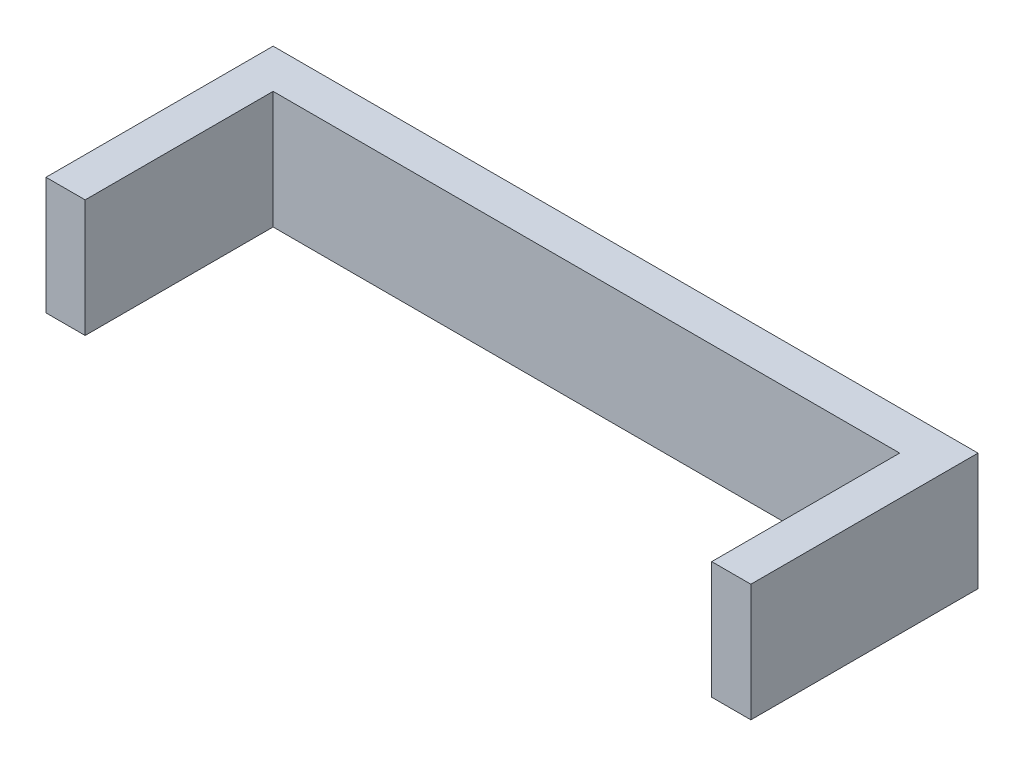
SolidWorks part; units mm, degrees
ref_plane "Front Plane" through (0, 0, 0) normal (0, 0, 1) x (1, 0, 0)
ref_plane "Top Plane" through (0, 0, 0) normal (0, 1, 0) x (1, 0, 0)
ref_plane "Right Plane" through (0, 0, 0) normal (1, 0, 0) x (0, 0, -1)
sketch "Sketch1" plane through (0, 0, 0) normal (0, 1, 0) x (1, 0, 0)
  line L0 (-35, 50) -> (35, 50)
  line L5 (50, 35) -> (50, -35)
  line L6 (-50, 35) -> (-50, -35)
  line L7 (-35, -50) -> (35, -50)
  arc A0 (35, -50) -> (50, -35) centre (35, -35) ccw
  arc A1 (-50, -35) -> (-35, -50) centre (-35, -35) ccw
  arc A2 (-50, 35) -> (-35, 50) centre (-35, 35) cw
  arc A3 (35, 50) -> (50, 35) centre (35, 35) cw
  point P14 (0, -50)
  point P19 (-50, 0)
  dimension "D3" = 15
  dimension "D4" = 15
  dimension "D5" = 15
  dimension "D6" = 15
  dimension "D1" = 100
  dimension "D2" = 100
extrude "Boss-Extrude1" add sketch "Sketch1" along normal blind 10
sketch "Sketch2" plane through (0, 10, 0) normal (0, 1, 0) x (1, 0, 0)
  line L0 (-50, 35) -> (-50, -35) construction
  line L1 (-42, 40) -> (-24.8, 40)
  line L2 (-42, 40) -> (-42, -3)
  line L3 (-42, -3) -> (-24.8, -3)
  line L4 (-24.8, 40) -> (-24.8, -3)
  line L5 (-42, 40) -> (-24.8, -3) construction
  line L6 (-42, -3) -> (-24.8, 40) construction
  line L7 (24.8, 40) -> (42, 40)
  line L8 (24.8, 40) -> (24.8, -3)
  line L9 (24.8, -3) -> (42, -3)
  line L10 (42, 40) -> (42, -3)
  line L11 (24.8, 40) -> (42, -3) construction
  line L12 (24.8, -3) -> (42, 40) construction
  line L13 (50, -35) -> (50, 35) construction
  line L15 (35, 50) -> (-35, 50) construction
  point P0 (-33.4, 18.5)
  point P5 (33.4, 18.5)
  dimension "D1" = 8
  dimension "D2" = 8
  dimension "D3" = 17.2
  dimension "D4" = 17.2
  dimension "D5" = 43
  dimension "D6" = 43
  dimension "D7" = 10
  dimension "D8" = 10
extrude "Cut-Extrude1" cut sketch "Sketch2" against normal through all
sketch "Sketch3" plane through (0, 10, 0) normal (0, 1, 0) x (1, 0, 0)
  line L1 (-40, -8) -> (40, -8)
  line L2 (-40, -8) -> (-40, -32)
  line L3 (-40, -32) -> (40, -32)
  line L4 (40, -8) -> (40, -32)
  line L5 (-40, -8) -> (40, -32) construction
  line L6 (-40, -32) -> (40, -8) construction
  line L7 (-45, -3) -> (45, -3)
  line L8 (-45, -3) -> (-45, -37)
  line L9 (-45, -37) -> (45, -37)
  line L10 (45, -3) -> (45, -37)
  line L11 (-45, -3) -> (45, -37) construction
  line L12 (-45, -37) -> (45, -3) construction
  line L13 (-35, -50) -> (35, -50) construction
  line L14 (-42, -3) -> (-24.8, -3) construction
  point P0 (0, -20)
  point P5 (0, -20)
  point P18 (0, -50)
  dimension "D1" = 24
  dimension "D2" = 80
  dimension "D3" = 34
  dimension "D4" = 90
extrude "Boss-Extrude3" add sketch "Sketch3" along normal blind 15
sketch "Sketch4" plane through (0, 10, 0) normal (0, 1, 0) x (1, 0, 0)
  line L0 (24.8, 40) -> (24.8, -3) construction
  line L3 (-24.8, 12.5) -> (24.8, 12.5)
  line L5 (-24.8, 24.5) -> (24.8, 24.5)
  line L6 (-24.8, 29.5) -> (24.8, 29.5)
  line L11 (-24.8, 7.5) -> (24.8, 7.5)
  line L12 (-24.8, 29.5) -> (-24.8, 24.5)
  line L13 (-24.8, -3) -> (-24.8, 40) construction
  line L14 (-24.8, 12.5) -> (-24.8, 7.5)
  line L15 (24.8, 12.5) -> (24.8, 7.5)
  line L16 (24.8, 29.5) -> (24.8, 24.5)
  point P4 (-24.8, 18.5)
  dimension "D1" = 5
  dimension "D2" = 12
  dimension "D3" = 5
  dimension "D4" = 6
extrude "Boss-Extrude4" add sketch "Sketch4" along normal blind 10
sketch "Sketch5" plane through (0, 20, 0) normal (0, 1, 0) x (1, 0, 0)
  line L0 (-24.8, 7.5) -> (24.8, 7.5) construction
  line L1 (-24.8, 29.5) -> (-9.8, 29.5)
  line L2 (-24.8, 29.5) -> (-24.8, 7.5)
  line L3 (-24.8, 7.5) -> (-9.8, 7.5)
  line L4 (-9.8, 29.5) -> (-9.8, 7.5)
  line L6 (24.8, 29.5) -> (9.8, 29.5)
  line L7 (24.8, 29.5) -> (24.8, 7.5)
  line L8 (24.8, 7.5) -> (9.8, 7.5)
  line L9 (9.8, 29.5) -> (9.8, 7.5)
  dimension "D1" = 15
  dimension "D2" = 15
extrude "Boss-Extrude5" add sketch "Sketch5" along normal blind 5
sketch "Sketch6" plane through (0, 10, 0) normal (0, 1, 0) x (1, 0, 0)
  line L1 (-45, -37) -> (45, -37)
  line L2 (-45, -37) -> (-45, 40)
  line L3 (-45, 40) -> (45, 40)
  line L4 (45, -37) -> (45, 40)
  line L5 (45, -37) -> (45, -3) construction
  line L6 (-24.8, 40) -> (-42, 40) construction
  line L7 (-50, 35) -> (-50, -35) construction
  line L8 (-35, -50) -> (35, -50) construction
  line L9 (50, -35) -> (50, 35) construction
  line L10 (35, 50) -> (-35, 50) construction
  line L11 (-50, 35) -> (-50, -35)
  line L12 (-35, -50) -> (35, -50)
  line L13 (50, -35) -> (50, 35)
  line L14 (35, 50) -> (-35, 50)
  arc A0 (-50, -35) -> (-35, -50) centre (-35, -35) ccw construction
  arc A1 (35, -50) -> (50, -35) centre (35, -35) ccw construction
  arc A2 (50, 35) -> (35, 50) centre (35, 35) ccw construction
  arc A3 (-35, 50) -> (-50, 35) centre (-35, 35) ccw construction
  arc A4 (-50, -35) -> (-35, -50) centre (-35, -35) ccw
  arc A5 (35, -50) -> (50, -35) centre (35, -35) ccw
  arc A6 (50, 35) -> (35, 50) centre (35, 35) ccw
  arc A7 (-35, 50) -> (-50, 35) centre (-35, 35) ccw
extrude "Boss-Extrude6" add sketch "Sketch6" along normal up to surface (15 mm away) up to face at (0, 25, 20)
sketch "Sketch9" plane through (0, 25, 0) normal (0, 1, 0) x (1, 0, 0)
  line L22 (-50, 35) -> (-50, -35) construction
  line L23 (-35, -50) -> (35, -50) construction
  line L24 (50, -35) -> (50, 35) construction
  line L25 (35, 50) -> (-35, 50) construction
  line L26 (-45, 35) -> (-45, -35)
  line L27 (-35, -45) -> (35, -45)
  line L28 (45, -35) -> (45, 35)
  line L29 (35, 45) -> (-35, 45)
  line L30 (-45, 35) -> (-45, -32)
  line L32 (45, -32) -> (45, 35)
  line L34 (-50, 35) -> (-50, -35)
  line L35 (-35, -50) -> (35, -50)
  line L36 (50, -35) -> (50, 35)
  line L37 (35, 50) -> (-35, 50)
  line L38 (45, -32) -> (-45, -32)
  line L39 (-40, -32) -> (40, -32) construction
  line L40 (43.6603, 40) -> (-43.6603, 40)
  line L41 (45, 40) -> (-45, 40) construction
  arc A23 (-50, -35) -> (-35, -50) centre (-35, -35) ccw construction
  arc A24 (35, -50) -> (50, -35) centre (35, -35) ccw construction
  arc A25 (50, 35) -> (35, 50) centre (35, 35) ccw construction
  arc A26 (-35, 50) -> (-50, 35) centre (-35, 35) ccw construction
  arc A27 (-45, -35) -> (-35, -45) centre (-35, -35) ccw
  arc A28 (35, -45) -> (45, -35) centre (35, -35) ccw
  arc A29 (45, 35) -> (35, 45) centre (35, 35) ccw
  arc A30 (-35, 45) -> (-45, 35) centre (-35, 35) ccw
  arc A33 (45, 35) -> (43.6603, 40) centre (35, 35) ccw
  arc A34 (-43.6603, 40) -> (-45, 35) centre (-35, 35) ccw
  arc A35 (-50, -35) -> (-35, -50) centre (-35, -35) ccw
  arc A36 (35, -50) -> (50, -35) centre (35, -35) ccw
  arc A37 (50, 35) -> (35, 50) centre (35, 35) ccw
  arc A38 (-35, 50) -> (-50, 35) centre (-35, 35) ccw
  dimension "D1" = 5
extrude "Boss-Extrude8" add sketch "Sketch9" along normal blind 39
chamfer "Chamfer1" distance 64 angle 3 8 edges at (0, 64, 50) (45.6066, 64, 45.6066) (-45.6066, 64, 45.6066) (50, 64, 0) (-50, 64, 0) (45.6066, 64, -45.6066) (-45.6066, 64, -45.6066) (0, 64, -50) first distance on face at (0, 32, 50) first distance on face at (44.0533, 32, 44.0533) first distance on face at (-44.0533, 32, 44.0533) first distance on face at (50, 32, 0) first distance on face at (-50, 32, 0) first distance on face at (44.0533, 32, -44.0533) first distance on face at (-44.0533, 32, -44.0533) first distance on face at (0, 32, -50)
chamfer "Chamfer2" distance 64 angle 10 1 edges at (0, 64, -46.6459) tangent propagation no first distance on face at (0, 32, -48.323)
chamfer "Chamfer3" distance 64 angle 12 1 edges at (0, 64, 46.6459) tangent propagation no first distance on face at (0, 32, 48.323)
sketch "Sketch10" plane through (0, 1.3075, 0) normal (-1, 0, 0) x (0, 0, 1)
  line L0 (-35, 62.6925) -> (32.8702, 62.6925) construction
  line L1 (2.8702, 62.6925) -> (-47.1298, 62.6925)
  line L2 (2.8702, 62.6925) -> (2.8702, 35.6925)
  line L3 (2.8702, 35.6925) -> (-47.1298, 35.6925)
  line L4 (-47.1298, 62.6925) -> (-47.1298, 35.6925)
  dimension "D1" = 50
  dimension "D2" = 27
  dimension "D3" = 30
extrude "Cut-Extrude3" cut sketch "Sketch10" against normal through all and the other way through all
sketch "Sketch11" plane through (0, 10, 0) normal (0, 1, 0) x (1, 0, 0)
  line L0 (24.8, 29.5) -> (-24.8, 29.5) construction
  line L1 (-22.75, 29.5) -> (22.75, 29.5)
  line L2 (-22.75, 29.5) -> (-22.75, 40)
  line L3 (-22.75, 40) -> (22.75, 40)
  line L4 (22.75, 29.5) -> (22.75, 40)
  line L5 (43.6603, 40) -> (-43.6603, 40) construction
  line L9 (24.8, 40) -> (-24.8, 40) construction
  point P10 (0, 40)
  point P11 (0, 29.5)
  dimension "D1" = 45.5
extrude "Cut-Extrude4" cut sketch "Sketch11" against normal blind 7.5
sketch "Sketch14" plane through (0, 10, 0) normal (0, 1, 0) x (1, 0, 0)
  line L0 (-24.8, 29.5) -> (-22.75, 29.5) construction
  line L1 (-22.75, 29.5) -> (-22.75, 40) construction
  line L2 (-22.75, 40) -> (-24.8, 40) construction
  line L3 (-24.8, 40) -> (-24.8, 29.5) construction
  line L4 (24.8, 40) -> (22.75, 40) construction
  line L5 (22.75, 40) -> (22.75, 29.5) construction
  line L6 (22.75, 29.5) -> (24.8, 29.5) construction
  line L7 (24.8, 29.5) -> (24.8, 40) construction
  line L8 (-24.8, 29.5) -> (-22.75, 29.5)
  line L9 (-22.75, 29.5) -> (-22.75, 40)
  line L10 (-22.75, 40) -> (-24.8, 40)
  line L11 (-24.8, 40) -> (-24.8, 29.5)
  line L12 (24.8, 40) -> (22.75, 40)
  line L13 (22.75, 40) -> (22.75, 29.5)
  line L14 (22.75, 29.5) -> (24.8, 29.5)
  line L15 (24.8, 29.5) -> (24.8, 40)
extrude "Boss-Extrude9" add sketch "Sketch14" along normal up to surface (15 mm away) up to face at (-17.3, 25, -18.5)
sketch "Sketch15" plane through (0, 0, -40) normal (0, 0, 1) x (1, 0, 0)
  line L0 (22.75, 2.5) -> (-22.75, 2.5) construction
  line L1 (12.75, 12.75) -> (-12.75, 12.75) construction
  line L2 (0, -35.2) -> (0, 35.2) construction
  circle A0 centre (-12.75, 12.75) radius 8
  circle A1 centre (12.75, 12.75) radius 8
  point P9 (0, 12.75)
  dimension "D3" = 16
  dimension "D4" = 16
  dimension "D1" = 10.25
  dimension "D2" = 10.25
  dimension "D5" = 25.5
extrude "Cut-Extrude5" cut sketch "Sketch15" against normal through all
sketch "Sketch17" plane through (0, 0, -29.5) normal (0, 0, -1) x (-1, 0, 0)
  line L8 (-9.8, 25) -> (-22.75, 25)
  line L9 (-22.75, 25) -> (-22.75, 2.5)
  line L10 (-22.75, 2.5) -> (22.75, 2.5)
  line L11 (22.75, 2.5) -> (22.75, 25)
  line L12 (22.75, 25) -> (9.8, 25)
  line L13 (9.8, 25) -> (9.8, 20)
  line L14 (9.8, 20) -> (-9.8, 20)
  line L15 (-9.8, 20) -> (-9.8, 25)
  line L16 (-9.8, 25) -> (-22.75, 25)
  line L17 (-22.75, 25) -> (-22.75, 2.5)
  line L18 (-22.75, 2.5) -> (22.75, 2.5)
  line L19 (22.75, 2.5) -> (22.75, 25)
  line L20 (22.75, 25) -> (9.8, 25)
  line L21 (9.8, 25) -> (9.8, 20)
  line L22 (9.8, 20) -> (-9.8, 20)
  line L23 (-9.8, 20) -> (-9.8, 25)
  dimension "D1" = 0
extrude "Cut-Extrude6" cut sketch "Sketch17" against normal blind 2.5
sketch "Sketch18" plane through (0, 0, 0) normal (0, -1, 0) x (1, 0, 0)
  line L1 (-14.8, -27) -> (14.8, -27)
  line L2 (-14.8, -27) -> (-14.8, 18)
  line L3 (-14.8, 18) -> (14.8, 18)
  line L4 (14.8, -27) -> (14.8, 18)
  line L5 (-24.8, 3) -> (-24.8, -40) construction
  line L6 (24.8, -40) -> (24.8, 3) construction
  line L8 (22.75, -27) -> (-22.75, -27) construction
  line L9 (24.8, 3) -> (42, 3) construction
  dimension "D1" = 10
  dimension "D2" = 10
  dimension "D3" = 15
extrude "Cut-Extrude7" cut sketch "Sketch18" against normal up to surface (10 mm away) up to face at (0, 10, -18.5)
sketch "Sketch20" plane through (0, 25, 0) normal (0, -1, 0) x (1, 0, 0)
  line L0 (-45, -35) -> (-45, -40) construction
  line L1 (-45, -40) -> (-43.6603, -40) construction
  line L2 (45, -40) -> (45, -35) construction
  line L3 (43.6603, -40) -> (45, -40) construction
  line L4 (-45, -35) -> (-45, -40)
  line L5 (-45, -40) -> (-43.6603, -40)
  line L6 (45, -40) -> (45, -35)
  line L7 (43.6603, -40) -> (45, -40)
  arc A0 (-45, -35) -> (-43.6603, -40) centre (-35, -35) ccw construction
  arc A1 (43.6603, -40) -> (45, -35) centre (35, -35) ccw construction
  arc A2 (-45, -35) -> (-43.6603, -40) centre (-35, -35) ccw
  arc A3 (43.6603, -40) -> (45, -35) centre (35, -35) ccw
extrude "Cut-Extrude8" cut sketch "Sketch20" against normal blind 15
sketch "Sketch21" plane through (0, 0, 0) normal (0, -1, 0) x (1, 0, 0)
  line L0 (-14.8, 18) -> (-14.8, -27) construction
  line L1 (-14.8, 3) -> (14.8, 3)
  line L2 (-14.8, 3) -> (-14.8, -12)
  line L3 (-14.8, -12) -> (14.8, -12)
  line L4 (14.8, 3) -> (14.8, -12)
  line L5 (14.8, -27) -> (14.8, 18) construction
  line L6 (14.8, 18) -> (-14.8, 18) construction
  line L7 (-14.8, -27) -> (14.8, -27) construction
  dimension "D1" = 15
  dimension "D2" = 15
extrude "Boss-Extrude10" add sketch "Sketch21" against normal blind 2.5
sketch "Sketch22" plane through (0, 64, 0) normal (0, 1, 0) x (1, 0, 0)
  line L0 (-45, 40) -> (-45, -32)
  line L1 (-45, -32) -> (45, -32)
  line L2 (45, -32) -> (45, 40)
  line L3 (45, 40) -> (-45, 40)
extrude "Cut-Extrude9" cut sketch "Sketch22" against normal up to surface (64 mm away) flip side to cut up to face at (0, 0, -19.5)
sketch "Sketch23" plane through (0, 0, 0) normal (0, -1, 0) x (1, 0, 0)
  line L12 (-24.8, 3) -> (-24.8, -40)
  line L13 (-24.8, -40) -> (24.8, -40)
  line L14 (24.8, -40) -> (24.8, 3)
  line L15 (24.8, 3) -> (42, 3)
  line L16 (42, 3) -> (42, -40)
  line L17 (42, -40) -> (45, -40)
  line L18 (45, -40) -> (45, 32)
  line L19 (45, 32) -> (-45, 32)
  line L20 (-45, 32) -> (-45, -40)
  line L21 (-45, -40) -> (-42, -40)
  line L22 (-42, -40) -> (-42, 3)
  line L23 (-42, 3) -> (-24.8, 3)
  line L24 (-24.8, 3) -> (-24.8, -40)
  line L25 (-24.8, -40) -> (24.8, -40)
  line L26 (24.8, -40) -> (24.8, 3)
  line L27 (24.8, 3) -> (42, 3)
  line L28 (42, 3) -> (42, -40)
  line L29 (42, -40) -> (45, -40)
  line L30 (45, -40) -> (45, 32)
  line L31 (45, 32) -> (-45, 32)
  line L32 (-45, 32) -> (-45, -40)
  line L33 (-45, -40) -> (-42, -40)
  line L34 (-42, -40) -> (-42, 3)
  line L35 (-42, 3) -> (-24.8, 3)
  dimension "D1" = 0
extrude "Cut-Extrude10" cut sketch "Sketch23" against normal up to surface (10 mm away) up to face at (19.8, 10, -2.25)
delete or keep bodies "-2" type delete bodies bodies 123
